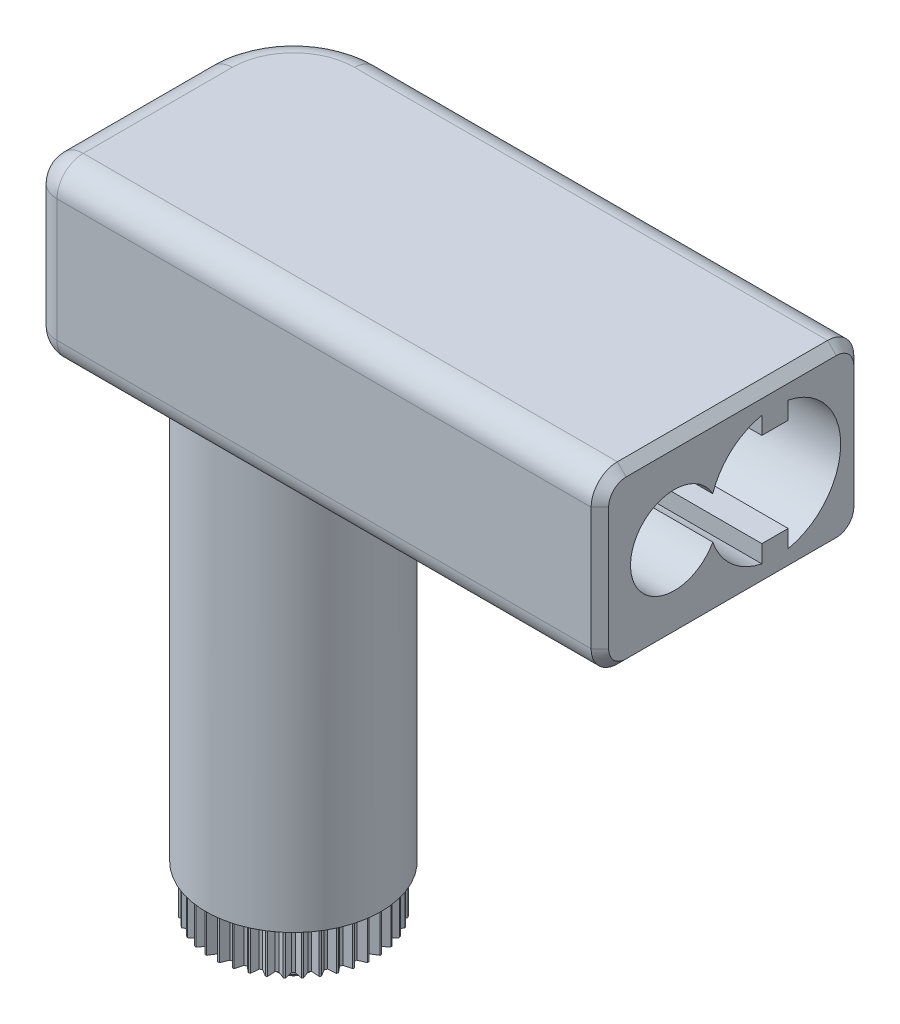
SolidWorks part; units mm, degrees
ref_plane "Front" through (0, 0, 0) normal (0, 0, 1) x (1, 0, 0)
ref_plane "Top" through (0, 0, 0) normal (0, 1, 0) x (1, 0, 0)
ref_plane "Right" through (0, 0, 0) normal (1, 0, 0) x (0, 0, -1)
sketch "Sketch1" plane through (0, 0, 0) normal (0, 1, 0) x (1, 0, 0)
  line L1 (-15, -20) -> (15, -20)
  line L2 (-15, -20) -> (-15, 20)
  line L3 (-15, 20) -> (15, 20)
  line L4 (15, -20) -> (15, 20)
  line L5 (-15, -20) -> (15, 20) construction
  line L6 (-15, 20) -> (15, -20) construction
  point P0 (0, 0)
extrude "Boss-Extrude1" add sketch "Sketch1" along normal blind 3
fillet "Fillet1" radius 5 4 edges at (-15, 1.5, -20) (15, 1.5, -20) (15, 1.5, 20) (-15, 1.5, 20)
chamfer "Chamfer1" distance 0.5 angle 45 16 edges at (-15, 0, 0) (-13.5355, 0, 18.5355) (-13.5355, 0, -18.5355) (0, 0, 20) (0, 0, -20) (13.5355, 0, 18.5355) (13.5355, 0, -18.5355) (15, 0, 0) (-15, 3, 0) (-13.5355, 3, 18.5355) (-13.5355, 3, -18.5355) (0, 3, 20) (0, 3, -20) (13.5355, 3, 18.5355) (13.5355, 3, -18.5355) (15, 3, 0)
sketch "Sketch2" plane through (0, 3, 0) normal (0, 1, 0) x (1, 0, 0)
  line L0 (0, 21.3573) -> (0, 0) construction
  line L1 (0, 0) -> (-23.5171, 0) construction
  circle A0 centre (-10, 15) radius 2.5
  circle A1 centre (10, 15) radius 2.5
  circle A2 centre (10, -15) radius 2.5
  circle A3 centre (-10, -15) radius 2.5
extrude "Cut-Extrude1" cut sketch "Sketch2" against normal through all
sketch "Sketch3" plane through (0, 3, 0) normal (0, 1, 0) x (1, 0, 0)
  circle A0 centre (-10, 15) radius 4
  circle A1 centre (10, 15) radius 4
  circle A2 centre (10, -15) radius 4
  circle A3 centre (-10, -15) radius 4
extrude "Cut-Extrude2" cut sketch "Sketch3" against normal blind 1
sketch "Sketch4" plane through (0, 3, 0) normal (0, 1, 0) x (1, 0, 0)
  circle A0 centre (0, 0) radius 10
extrude "Boss-Extrude2" add sketch "Sketch4" along normal blind 100
sketch "Sketch5" plane through (0, 103, 0) normal (0, 1, 0) x (1, 0, 0)
  line L0 (0, 10) -> (55, 10)
  line L1 (55, 10) -> (55, -20)
  line L3 (55, -20) -> (-10, -20)
  line L4 (-10, -20) -> (-10, 0)
  circle A0 centre (0, 0) radius 10 construction
  circle A3 centre (0, 0) radius 10 construction
  arc A4 (-10, 0) -> (0, 10) centre (0, 0) cw
extrude "Boss-Extrude3" add sketch "Sketch5" against normal blind 20
sketch "Sketch6" plane through (55, 0, 0) normal (1, 0, 0) x (0, 0, -1)
  line L5 (-7, 86) -> (7, 100) construction
  line L6 (-7, 100) -> (7, 86) construction
  line L7 (-20, 103) -> (10, 103) construction
  line L8 (0, 104.5972) -> (0, 79.2989) construction
  line L13 (-12.2624, 93) -> (16.6416, 93) construction
  line L14 (10, 83) -> (10, 103) construction
  line L19 (-1.5, 100.3485) -> (-1.5, 98.3485)
  line L25 (-1.5, 98.3485) -> (1.5, 98.3485)
  line L26 (1.5, 98.3485) -> (1.5, 100.3485)
  line L27 (-1.5, 87.6515) -> (1.5, 87.6515)
  line L28 (-1.5, 85.6515) -> (-1.5, 87.6515)
  line L29 (1.5, 87.6515) -> (1.5, 85.6515)
  circle A0 centre (-11.5, 93) radius 5 construction
  circle A1 centre (0, 93) radius 7.5 construction
  arc A3 (-7.1087, 95.3909) -> (-7.1087, 90.6091) centre (-11.5, 93) ccw
  arc A4 (-1.5, 100.3485) -> (-7.1087, 95.3909) centre (0, 93) ccw
  arc A5 (-7.1087, 90.6091) -> (-1.5, 85.6515) centre (0, 93) ccw
  arc A7 (1.5, 100.3485) -> (1.5, 85.6515) centre (0, 93) cw
  point P0 (0, 93)
  dimension "D4" = 1.5
  dimension "D3" = 11.5
  dimension "D1" = 10
  dimension "D2" = 10
extrude "Cut-Extrude3" cut sketch "Sketch6" against normal blind 65
fillet "Fillet3" radius 3 8 edges at (-10, 103, 10) (-7.0711, 103, -7.0711) (27.5, 83, -10) (-10, 83, 10) (22.5, 83, 20) (-10, 93, 20) (22.5, 103, 20) (27.5, 103, -10)
chamfer "Chamfer2" distance 1 angle 45 8 edges at (55, 83.8787, 19.1213) (55, 93, 20) (55, 102.1213, 19.1213) (55, 103, 5) (55, 102.1213, -9.1213) (55, 93, -10) (55, 83.8787, -9.1213) (55, 83, 5)
sketch "Sketch7" plane through (0, 0, 0) normal (0, 0, 1) x (1, 0, 0)
  line L0 (-25.177, 23) -> (21.6478, 23)
  line L1 (21.6478, 23) -> (21.6478, -7.0722)
  line L2 (21.6478, -7.0722) -> (-25.177, -7.0722)
  line L3 (-25.177, -7.0722) -> (-25.177, 23)
  line L4 (14.5, 3) -> (10, 3) construction
  dimension "D1" = 20
extrude "Cut-Extrude4" cut sketch "Sketch7" against normal through all both and the other way through all
sketch "Sketch8" plane through (0, 23, 0) normal (0, -1, 0) x (1, 0, 0)
  circle A0 centre (0, 0) radius 3
extrude "Boss-Extrude4" add sketch "Sketch8" along normal blind 1
sketch "Sketch9" plane through (0, 22, 0) normal (0, -1, 0) x (1, 0, 0)
  circle A0 centre (0, 0) radius 2.4
extrude "Boss-Extrude5" add sketch "Sketch9" along normal blind 4
chamfer "Chamfer3" distance 0.5 angle 45 1 edges at (0, 18, -2.4)
sketch "Sketch18" plane through (0, 23, 0) normal (0, -1, 0) x (1, 0, 0)
  line L0 (0, 12.7735) -> (0, 3.4857) construction
  line L133 (-0.6363, 9.2782) -> (-0.15, 8.5)
  line L134 (-0.15, 8.5) -> (0.15, 8.5)
  line L135 (0.15, 8.5) -> (0.6363, 9.2782)
  line L136 (0.6363, 9.2782) -> (0, 10.6682)
  line L137 (0, 10.6682) -> (-0.6363, 9.2782)
  line L138 (1.6689, 10.5368) -> (0.823, 9.2635)
  line L139 (0.823, 9.2635) -> (1.1815, 8.4188)
  line L140 (1.1815, 8.4188) -> (1.4778, 8.3719)
  line L141 (1.4778, 8.3719) -> (2.0799, 9.0644)
  line L142 (2.0799, 9.0644) -> (1.6689, 10.5368)
  line L143 (3.2966, 10.146) -> (2.262, 9.0207)
  line L144 (2.262, 9.0207) -> (2.484, 8.1303)
  line L145 (2.484, 8.1303) -> (2.7693, 8.0376)
  line L146 (2.7693, 8.0376) -> (3.4723, 8.6275)
  line L147 (3.4723, 8.6275) -> (3.2966, 10.146)
  line L148 (4.8432, 9.5054) -> (3.6453, 8.5558)
  line L149 (3.6453, 8.5558) -> (3.7253, 7.6417)
  line L150 (3.7253, 7.6417) -> (3.9926, 7.5055)
  line L151 (3.9926, 7.5055) -> (4.7791, 7.9781)
  line L152 (4.7791, 7.9781) -> (4.8432, 9.5054)
  line L153 (6.2706, 8.6307) -> (4.9388, 7.8802)
  line L154 (4.9388, 7.8802) -> (4.8748, 6.9648)
  line L155 (4.8748, 6.9648) -> (5.1175, 6.7885)
  line L156 (5.1175, 6.7885) -> (5.9684, 7.1322)
  line L157 (5.9684, 7.1322) -> (6.2706, 8.6307)
  line L158 (7.5435, 7.5435) -> (6.1108, 7.0106)
  line L159 (6.1108, 7.0106) -> (5.9043, 6.1165)
  line L160 (5.9043, 6.1165) -> (6.1165, 5.9043)
  line L161 (6.1165, 5.9043) -> (7.0106, 6.1108)
  line L162 (7.0106, 6.1108) -> (7.5435, 7.5435)
  line L163 (8.6307, 6.2706) -> (7.1322, 5.9684)
  line L164 (7.1322, 5.9684) -> (6.7885, 5.1175)
  line L165 (6.7885, 5.1175) -> (6.9648, 4.8748)
  line L166 (6.9648, 4.8748) -> (7.8802, 4.9388)
  line L167 (7.8802, 4.9388) -> (8.6307, 6.2706)
  line L168 (9.5054, 4.8432) -> (7.9781, 4.7791)
  line L169 (7.9781, 4.7791) -> (7.5055, 3.9926)
  line L170 (7.5055, 3.9926) -> (7.6417, 3.7253)
  line L171 (7.6417, 3.7253) -> (8.5558, 3.6453)
  line L172 (8.5558, 3.6453) -> (9.5054, 4.8432)
  line L173 (10.146, 3.2966) -> (8.6275, 3.4723)
  line L174 (8.6275, 3.4723) -> (8.0376, 2.7693)
  line L175 (8.0376, 2.7693) -> (8.1303, 2.484)
  line L176 (8.1303, 2.484) -> (9.0207, 2.262)
  line L177 (9.0207, 2.262) -> (10.146, 3.2966)
  line L178 (10.5368, 1.6689) -> (9.0644, 2.0799)
  line L179 (9.0644, 2.0799) -> (8.3719, 1.4778)
  line L180 (8.3719, 1.4778) -> (8.4188, 1.1815)
  line L181 (8.4188, 1.1815) -> (9.2635, 0.823)
  line L182 (9.2635, 0.823) -> (10.5368, 1.6689)
  line L183 (10.6682, 0) -> (9.2782, 0.6363)
  line L184 (9.2782, 0.6363) -> (8.5, 0.15)
  line L185 (8.5, 0.15) -> (8.5, -0.15)
  line L186 (8.5, -0.15) -> (9.2782, -0.6363)
  line L187 (9.2782, -0.6363) -> (10.6682, 0)
  line L188 (10.5368, -1.6689) -> (9.2635, -0.823)
  line L189 (9.2635, -0.823) -> (8.4188, -1.1815)
  line L190 (8.4188, -1.1815) -> (8.3719, -1.4778)
  line L191 (8.3719, -1.4778) -> (9.0644, -2.0799)
  line L192 (9.0644, -2.0799) -> (10.5368, -1.6689)
  line L193 (10.146, -3.2966) -> (9.0207, -2.262)
  line L194 (9.0207, -2.262) -> (8.1303, -2.484)
  line L195 (8.1303, -2.484) -> (8.0376, -2.7693)
  line L196 (8.0376, -2.7693) -> (8.6275, -3.4723)
  line L197 (8.6275, -3.4723) -> (10.146, -3.2966)
  line L198 (9.5054, -4.8432) -> (8.5558, -3.6453)
  line L199 (8.5558, -3.6453) -> (7.6417, -3.7253)
  line L200 (7.6417, -3.7253) -> (7.5055, -3.9926)
  line L201 (7.5055, -3.9926) -> (7.9781, -4.7791)
  line L202 (7.9781, -4.7791) -> (9.5054, -4.8432)
  line L203 (8.6307, -6.2706) -> (7.8802, -4.9388)
  line L204 (7.8802, -4.9388) -> (6.9648, -4.8748)
  line L205 (6.9648, -4.8748) -> (6.7885, -5.1175)
  line L206 (6.7885, -5.1175) -> (7.1322, -5.9684)
  line L207 (7.1322, -5.9684) -> (8.6307, -6.2706)
  line L208 (7.5435, -7.5435) -> (7.0106, -6.1108)
  line L209 (7.0106, -6.1108) -> (6.1165, -5.9043)
  line L210 (6.1165, -5.9043) -> (5.9043, -6.1165)
  line L211 (5.9043, -6.1165) -> (6.1108, -7.0106)
  line L212 (6.1108, -7.0106) -> (7.5435, -7.5435)
  line L213 (6.2706, -8.6307) -> (5.9684, -7.1322)
  line L214 (5.9684, -7.1322) -> (5.1175, -6.7885)
  line L215 (5.1175, -6.7885) -> (4.8748, -6.9648)
  line L216 (4.8748, -6.9648) -> (4.9388, -7.8802)
  line L217 (4.9388, -7.8802) -> (6.2706, -8.6307)
  line L218 (4.8432, -9.5054) -> (4.7791, -7.9781)
  line L219 (4.7791, -7.9781) -> (3.9926, -7.5055)
  line L220 (3.9926, -7.5055) -> (3.7253, -7.6417)
  line L221 (3.7253, -7.6417) -> (3.6453, -8.5558)
  line L222 (3.6453, -8.5558) -> (4.8432, -9.5054)
  line L223 (3.2966, -10.146) -> (3.4723, -8.6275)
  line L224 (3.4723, -8.6275) -> (2.7693, -8.0376)
  line L225 (2.7693, -8.0376) -> (2.484, -8.1303)
  line L226 (2.484, -8.1303) -> (2.262, -9.0207)
  line L227 (2.262, -9.0207) -> (3.2966, -10.146)
  line L228 (1.6689, -10.5368) -> (2.0799, -9.0644)
  line L229 (2.0799, -9.0644) -> (1.4778, -8.3719)
  line L230 (1.4778, -8.3719) -> (1.1815, -8.4188)
  line L231 (1.1815, -8.4188) -> (0.823, -9.2635)
  line L232 (0.823, -9.2635) -> (1.6689, -10.5368)
  line L233 (0, -10.6682) -> (0.6363, -9.2782)
  line L234 (0.6363, -9.2782) -> (0.15, -8.5)
  line L235 (0.15, -8.5) -> (-0.15, -8.5)
  line L236 (-0.15, -8.5) -> (-0.6363, -9.2782)
  line L237 (-0.6363, -9.2782) -> (0, -10.6682)
  line L238 (-1.6689, -10.5368) -> (-0.823, -9.2635)
  line L239 (-0.823, -9.2635) -> (-1.1815, -8.4188)
  line L240 (-1.1815, -8.4188) -> (-1.4778, -8.3719)
  line L241 (-1.4778, -8.3719) -> (-2.0799, -9.0644)
  line L242 (-2.0799, -9.0644) -> (-1.6689, -10.5368)
  line L243 (-3.2966, -10.146) -> (-2.262, -9.0207)
  line L244 (-2.262, -9.0207) -> (-2.484, -8.1303)
  line L245 (-2.484, -8.1303) -> (-2.7693, -8.0376)
  line L246 (-2.7693, -8.0376) -> (-3.4723, -8.6275)
  line L247 (-3.4723, -8.6275) -> (-3.2966, -10.146)
  line L248 (-4.8432, -9.5054) -> (-3.6453, -8.5558)
  line L249 (-3.6453, -8.5558) -> (-3.7253, -7.6417)
  line L250 (-3.7253, -7.6417) -> (-3.9926, -7.5055)
  line L251 (-3.9926, -7.5055) -> (-4.7791, -7.9781)
  line L252 (-4.7791, -7.9781) -> (-4.8432, -9.5054)
  line L253 (-6.2706, -8.6307) -> (-4.9388, -7.8802)
  line L254 (-4.9388, -7.8802) -> (-4.8748, -6.9648)
  line L255 (-4.8748, -6.9648) -> (-5.1175, -6.7885)
  line L256 (-5.1175, -6.7885) -> (-5.9684, -7.1322)
  line L257 (-5.9684, -7.1322) -> (-6.2706, -8.6307)
  line L258 (-7.5435, -7.5435) -> (-6.1108, -7.0106)
  line L259 (-6.1108, -7.0106) -> (-5.9043, -6.1165)
  line L260 (-5.9043, -6.1165) -> (-6.1165, -5.9043)
  line L261 (-6.1165, -5.9043) -> (-7.0106, -6.1108)
  line L262 (-7.0106, -6.1108) -> (-7.5435, -7.5435)
  line L263 (-8.6307, -6.2706) -> (-7.1322, -5.9684)
  line L264 (-7.1322, -5.9684) -> (-6.7885, -5.1175)
  line L265 (-6.7885, -5.1175) -> (-6.9648, -4.8748)
  line L266 (-6.9648, -4.8748) -> (-7.8802, -4.9388)
  line L267 (-7.8802, -4.9388) -> (-8.6307, -6.2706)
  line L268 (-9.5054, -4.8432) -> (-7.9781, -4.7791)
  line L269 (-7.9781, -4.7791) -> (-7.5055, -3.9926)
  line L270 (-7.5055, -3.9926) -> (-7.6417, -3.7253)
  line L271 (-7.6417, -3.7253) -> (-8.5558, -3.6453)
  line L272 (-8.5558, -3.6453) -> (-9.5054, -4.8432)
  line L273 (-10.146, -3.2966) -> (-8.6275, -3.4723)
  line L274 (-8.6275, -3.4723) -> (-8.0376, -2.7693)
  line L275 (-8.0376, -2.7693) -> (-8.1303, -2.484)
  line L276 (-8.1303, -2.484) -> (-9.0207, -2.262)
  line L277 (-9.0207, -2.262) -> (-10.146, -3.2966)
  line L278 (-10.5368, -1.6689) -> (-9.0644, -2.0799)
  line L279 (-9.0644, -2.0799) -> (-8.3719, -1.4778)
  line L280 (-8.3719, -1.4778) -> (-8.4188, -1.1815)
  line L281 (-8.4188, -1.1815) -> (-9.2635, -0.823)
  line L282 (-9.2635, -0.823) -> (-10.5368, -1.6689)
  line L283 (-10.6682, 0) -> (-9.2782, -0.6363)
  line L284 (-9.2782, -0.6363) -> (-8.5, -0.15)
  line L285 (-8.5, -0.15) -> (-8.5, 0.15)
  line L286 (-8.5, 0.15) -> (-9.2782, 0.6363)
  line L287 (-9.2782, 0.6363) -> (-10.6682, 0)
  line L288 (-10.5368, 1.6689) -> (-9.2635, 0.823)
  line L289 (-9.2635, 0.823) -> (-8.4188, 1.1815)
  line L290 (-8.4188, 1.1815) -> (-8.3719, 1.4778)
  line L291 (-8.3719, 1.4778) -> (-9.0644, 2.0799)
  line L292 (-9.0644, 2.0799) -> (-10.5368, 1.6689)
  line L293 (-10.146, 3.2966) -> (-9.0207, 2.262)
  line L294 (-9.0207, 2.262) -> (-8.1303, 2.484)
  line L295 (-8.1303, 2.484) -> (-8.0376, 2.7693)
  line L296 (-8.0376, 2.7693) -> (-8.6275, 3.4723)
  line L297 (-8.6275, 3.4723) -> (-10.146, 3.2966)
  line L298 (-9.5054, 4.8432) -> (-8.5558, 3.6453)
  line L299 (-8.5558, 3.6453) -> (-7.6417, 3.7253)
  line L300 (-7.6417, 3.7253) -> (-7.5055, 3.9926)
  line L301 (-7.5055, 3.9926) -> (-7.9781, 4.7791)
  line L302 (-7.9781, 4.7791) -> (-9.5054, 4.8432)
  line L303 (-8.6307, 6.2706) -> (-7.8802, 4.9388)
  line L304 (-7.8802, 4.9388) -> (-6.9648, 4.8748)
  line L305 (-6.9648, 4.8748) -> (-6.7885, 5.1175)
  line L306 (-6.7885, 5.1175) -> (-7.1322, 5.9684)
  line L307 (-7.1322, 5.9684) -> (-8.6307, 6.2706)
  line L308 (-7.5435, 7.5435) -> (-7.0106, 6.1108)
  line L309 (-7.0106, 6.1108) -> (-6.1165, 5.9043)
  line L310 (-6.1165, 5.9043) -> (-5.9043, 6.1165)
  line L311 (-5.9043, 6.1165) -> (-6.1108, 7.0106)
  line L312 (-6.1108, 7.0106) -> (-7.5435, 7.5435)
  line L313 (-6.2706, 8.6307) -> (-5.9684, 7.1322)
  line L314 (-5.9684, 7.1322) -> (-5.1175, 6.7885)
  line L315 (-5.1175, 6.7885) -> (-4.8748, 6.9648)
  line L316 (-4.8748, 6.9648) -> (-4.9388, 7.8802)
  line L317 (-4.9388, 7.8802) -> (-6.2706, 8.6307)
  line L318 (-4.8432, 9.5054) -> (-4.7791, 7.9781)
  line L319 (-4.7791, 7.9781) -> (-3.9926, 7.5055)
  line L320 (-3.9926, 7.5055) -> (-3.7253, 7.6417)
  line L321 (-3.7253, 7.6417) -> (-3.6453, 8.5558)
  line L322 (-3.6453, 8.5558) -> (-4.8432, 9.5054)
  line L323 (-3.2966, 10.146) -> (-3.4723, 8.6275)
  line L324 (-3.4723, 8.6275) -> (-2.7693, 8.0376)
  line L325 (-2.7693, 8.0376) -> (-2.484, 8.1303)
  line L326 (-2.484, 8.1303) -> (-2.262, 9.0207)
  line L327 (-2.262, 9.0207) -> (-3.2966, 10.146)
  line L328 (-1.6689, 10.5368) -> (-2.0799, 9.0644)
  line L329 (-2.0799, 9.0644) -> (-1.4778, 8.3719)
  line L330 (-1.4778, 8.3719) -> (-1.1815, 8.4188)
  line L331 (-1.1815, 8.4188) -> (-0.823, 9.2635)
  line L332 (-0.823, 9.2635) -> (-1.6689, 10.5368)
  point P205 (0, 0)
extrude "Cut-Extrude5" cut sketch "Sketch18" against normal blind 5
sketch "Sketch19" plane through (0, 23, 0) normal (0, -1, 0) x (1, 0, 0)
  circle A0 centre (0, 0) radius 9.3
  circle A1 centre (0, 0) radius 10
extrude "Cut-Extrude6" cut sketch "Sketch19" against normal blind 5
